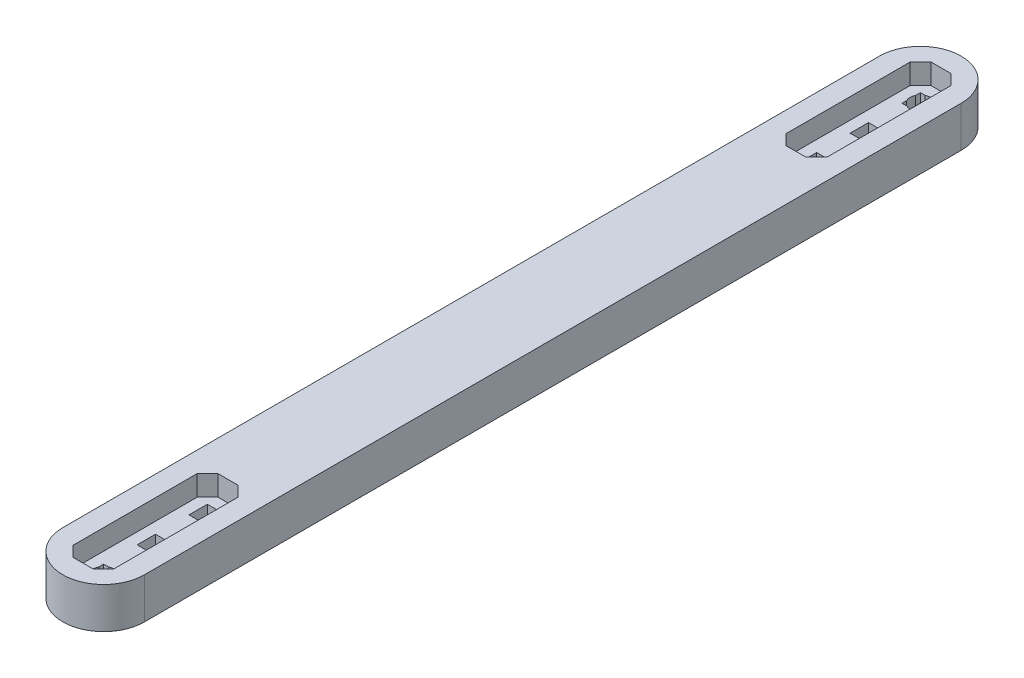
SolidWorks part; units mm, degrees
ref_plane "Front Plane" through (0, 0, 0) normal (0, 0, 1) x (1, 0, 0)
ref_plane "Top Plane" through (0, 0, 0) normal (0, 1, 0) x (1, 0, 0)
ref_plane "Right Plane" through (0, 0, 0) normal (1, 0, 0) x (0, 0, -1)
sketch "Sketch1" plane through (0, 0, 0) normal (0, 1, 0) x (1, 0, 0)
  line L0 (-10, 100) -> (10, 100) construction
  line L2 (10, -100) -> (10, 100)
  line L4 (-10, -100) -> (-10, 100)
  line L5 (10, -100) -> (-10, 100) construction
  line L6 (10, 100) -> (-10, -100) construction
  line L8 (-1.5875, 98.4125) -> (1.5875, 98.4125)
  line L9 (-1.5875, 98.4125) -> (-1.5875, 101.5875)
  line L10 (-1.5875, 101.5875) -> (1.5875, 101.5875)
  line L11 (1.5875, 98.4125) -> (1.5875, 101.5875)
  line L12 (-1.5875, 98.4125) -> (1.5875, 101.5875) construction
  line L13 (-1.5875, 101.5875) -> (1.5875, 98.4125) construction
  arc A0 (-10, 100) -> (10, 100) centre (0, 100) cw
  arc A1 (10, -100) -> (-10, -100) centre (0, -100) cw
  circle A2 centre (0, -100) radius 2.5
  circle A3 centre (0, 100) radius 2.2451
  point P0 (0, 0)
  dimension "D3" = 5
  dimension "D1" = 200
  dimension "D2" = 20
  dimension "D4" = 3.175
extrude "Boss-Extrude1" add sketch "Sketch1" along normal blind 10 contours A1 L2 A0 L4 A3 A2 region at (0, 0, -0.0888)
sketch "Sketch2" plane through (0, 10, 0) normal (0, 1, 0) x (1, 0, 0)
  line L0 (-5, -102.51) -> (-2.46, -105.05)
  line L1 (-2.46, -105.05) -> (2.46, -105.05)
  line L2 (-5, -102.51) -> (-5, -72.09)
  line L3 (-2.46, -69.55) -> (2.46, -69.55)
  line L4 (5, -102.51) -> (5, -72.09)
  line L5 (-5, -105.05) -> (5, -69.55) construction
  line L6 (-5, -69.55) -> (5, -105.05) construction
  line L7 (2.46, -105.05) -> (5, -102.51)
  line L8 (2.46, -69.55) -> (5, -72.09)
  line L9 (-5, -72.09) -> (-2.46, -69.55)
  line L10 (2.25, -72.35) -> (-2.25, -72.35)
  line L11 (2.25, -72.35) -> (2.25, -76.85)
  line L12 (2.25, -76.85) -> (-2.25, -76.85)
  line L13 (-2.25, -72.35) -> (-2.25, -76.85)
  line L14 (2.25, -72.35) -> (-2.25, -76.85) construction
  line L15 (2.25, -76.85) -> (-2.25, -72.35) construction
  line L16 (2.25, -85.05) -> (-2.25, -85.05)
  line L17 (2.25, -85.05) -> (2.25, -89.55)
  line L18 (2.25, -89.55) -> (-2.25, -89.55)
  line L19 (-2.25, -85.05) -> (-2.25, -89.55)
  line L20 (2.25, -85.05) -> (-2.25, -89.55) construction
  line L21 (2.25, -89.55) -> (-2.25, -85.05) construction
  line L22 (2.25, -97.75) -> (-2.25, -97.75)
  line L23 (2.25, -97.75) -> (2.25, -102.25)
  line L24 (2.25, -102.25) -> (-2.25, -102.25)
  line L25 (-2.25, -97.75) -> (-2.25, -102.25)
  line L26 (2.25, -97.75) -> (-2.25, -102.25) construction
  line L27 (2.25, -102.25) -> (-2.25, -97.75) construction
  line L28 (-10, 0) -> (10, 0) construction
  line L29 (-10, -100) -> (-10, 100) construction
  line L30 (10, -100) -> (10, 100) construction
  line L31 (2.25, 102.25) -> (-2.25, 97.75) construction
  line L32 (2.25, 97.75) -> (-2.25, 102.25) construction
  line L33 (2.25, 89.55) -> (-2.25, 85.05) construction
  line L34 (2.25, 85.05) -> (-2.25, 89.55) construction
  line L35 (2.25, 76.85) -> (-2.25, 72.35) construction
  line L36 (2.25, 72.35) -> (-2.25, 76.85) construction
  line L37 (-5, 69.55) -> (5, 105.05) construction
  line L38 (-5, 105.05) -> (5, 69.55) construction
  line L39 (-2.25, 97.75) -> (-2.25, 102.25)
  line L40 (2.25, 102.25) -> (-2.25, 102.25)
  line L41 (2.25, 97.75) -> (2.25, 102.25)
  line L42 (2.25, 97.75) -> (-2.25, 97.75)
  line L43 (-2.25, 85.05) -> (-2.25, 89.55)
  line L44 (2.25, 89.55) -> (-2.25, 89.55)
  line L45 (2.25, 85.05) -> (2.25, 89.55)
  line L46 (2.25, 85.05) -> (-2.25, 85.05)
  line L47 (-2.25, 72.35) -> (-2.25, 76.85)
  line L48 (2.25, 76.85) -> (-2.25, 76.85)
  line L49 (2.25, 72.35) -> (2.25, 76.85)
  line L50 (2.25, 72.35) -> (-2.25, 72.35)
  line L51 (-5, 72.09) -> (-2.46, 69.55)
  line L52 (2.46, 69.55) -> (5, 72.09)
  line L53 (2.46, 105.05) -> (5, 102.51)
  line L54 (5, 102.51) -> (5, 72.09)
  line L55 (-2.46, 69.55) -> (2.46, 69.55)
  line L56 (-5, 102.51) -> (-5, 72.09)
  line L57 (-2.46, 105.05) -> (2.46, 105.05)
  line L58 (-5, 102.51) -> (-2.46, 105.05)
  circle A0 centre (0, -100) radius 2.5
  circle A1 centre (0, 100) radius 2.5
  point P0 (0, -74.6)
  point P2 (0, -87.3)
  point P18 (0, -87.3)
  point P23 (0, -100)
  point P63 (0, 100)
  point P64 (0, 87.3)
  point P65 (0, 74.6)
  circle M20 centre (0, -100) radius 2.5
  dimension "D12" = 5
  dimension "D1" = 2.54
  dimension "D2" = 2.54
  dimension "D3" = 2.54
  dimension "D4" = 2.54
  dimension "D5" = 2.54
  dimension "D6" = 2.54
  dimension "D7" = 2.54
  dimension "D8" = 2.54
  dimension "D9" = 12.7
  dimension "D10" = 12.7
  dimension "D11" = 4.5
  dimension "D13" = 10
  dimension "D14" = 35.5
extrude "Cut-Extrude1" cut sketch "Sketch2" against normal blind 10 contours L25 L24 L23 L22 | A0 | L16 L19 L18 L17 | L12 L13 L10 L11 | L50 L47 L48 L49 | L46 L43 L44 L45 | L42 L39 L40 L41 | A1
extrude "Cut-Extrude2" cut sketch "Sketch2<3>" against normal blind 5 contours L9 L2 L0 L1 L7 L4 L8 L3 L25 L22 L23 L24 L19 L16 L17 L18 L13 L10 L11 L12 M20 | L58 L56 L51 L55 L52 L54 L53 L57 L45 L46 L43 L44 L49 L50 L47 L48 L39 A1 L40 L41 L42 region at (-4.6312, 10, 87.3) region at (-4.6312, 10, -87.3)
sketch "Sketch2<3>" plane through (0, 10, 0) normal (0, 1, 0) x (1, 0, 0) same geometry as "Sketch2"
